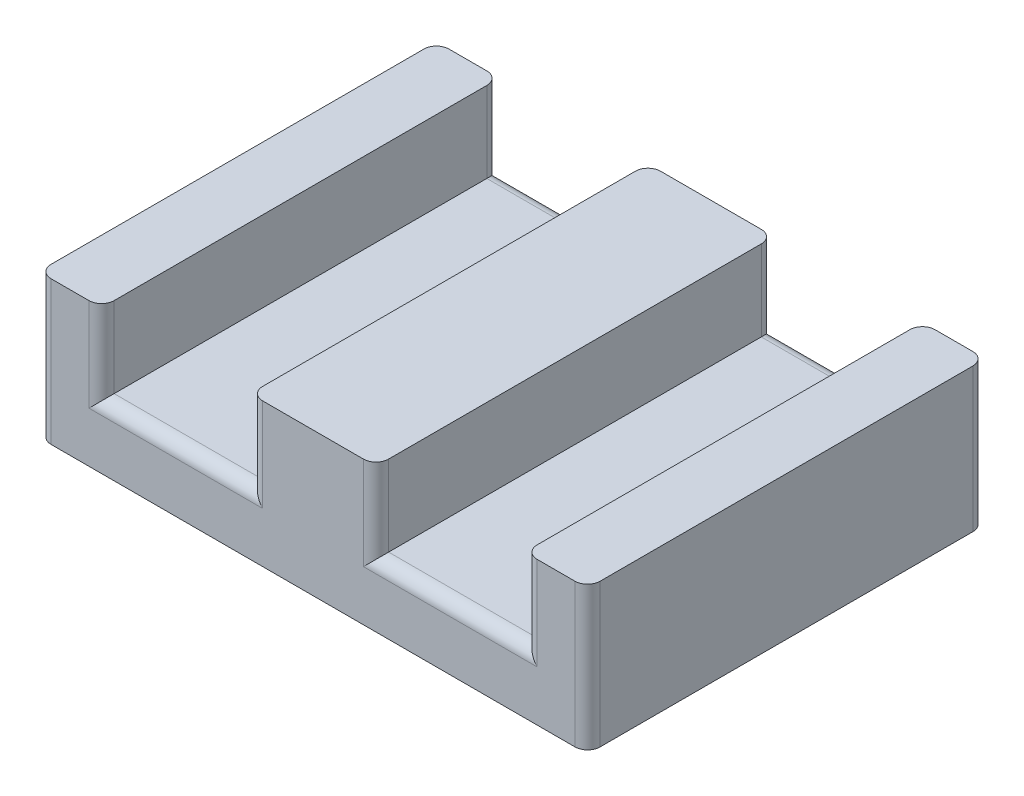
SolidWorks part; units mm, degrees
ref_plane "Спереди" through (0, 0, 0) normal (0, 0, 1) x (1, 0, 0)
ref_plane "Сверху" through (0, 0, 0) normal (0, 1, 0) x (1, 0, 0)
ref_plane "Справа" through (0, 0, 0) normal (1, 0, 0) x (0, 0, -1)
sketch "Эскиз1" plane through (0, 0, 0) normal (0, 0, 1) x (1, 0, 0)
  line L0 (0, 8.3092) -> (0, -6.0489) construction
  line L1 (-10.9, -2.9116) -> (10.9, -2.9116)
  line L2 (10.9, -2.9116) -> (10.9, 2.7884)
  line L3 (10.9, 2.7884) -> (8.4, 2.7884)
  line L4 (8.4, 2.7884) -> (8.4, -0.4116)
  line L5 (8.4, -0.4116) -> (2.5, -0.4116)
  line L6 (2.5, -0.4116) -> (2.5, 2.7884)
  line L7 (2.5, 2.7884) -> (-2.5, 2.7884)
  line L9 (-2.5, -0.4116) -> (-2.5, 2.7884)
  line L10 (-8.4, -0.4116) -> (-2.5, -0.4116)
  line L11 (-8.4, 2.7884) -> (-8.4, -0.4116)
  line L12 (-10.9, 2.7884) -> (-8.4, 2.7884)
  line L13 (-10.9, -2.9116) -> (-10.9, 2.7884)
  point P5 (0, 2.7884)
  point P17 (0, -2.9116)
  dimension "D1" = 10.9
  dimension "D2" = 5.7
  dimension "D3" = 3.2
  dimension "D4" = 2.5
  dimension "D5" = 8.4
extrude "Бобышка-Вытянуть1" add sketch "Эскиз1" along normal blind 7.9 and the other way blind 7.9
fillet "Скругление1" radius 0.5 16 edges at (10.9, -0.0616, 7.9) (8.4, 1.1884, 7.9) (5.45, -0.4116, 7.9) (2.5, 1.1884, 7.9) (-2.5, 1.1884, 7.9) (-5.45, -0.4116, 7.9) (-8.4, 1.1884, 7.9) (-10.9, -0.0616, 7.9) (-10.9, -0.0616, -7.9) (-8.4, 1.1884, -7.9) (-5.45, -0.4116, -7.9) (5.45, -0.4116, -7.9) (-2.5, 1.1884, -7.9) (2.5, 1.1884, -7.9) (8.4, 1.1884, -7.9) (10.9, -0.0616, -7.9)
